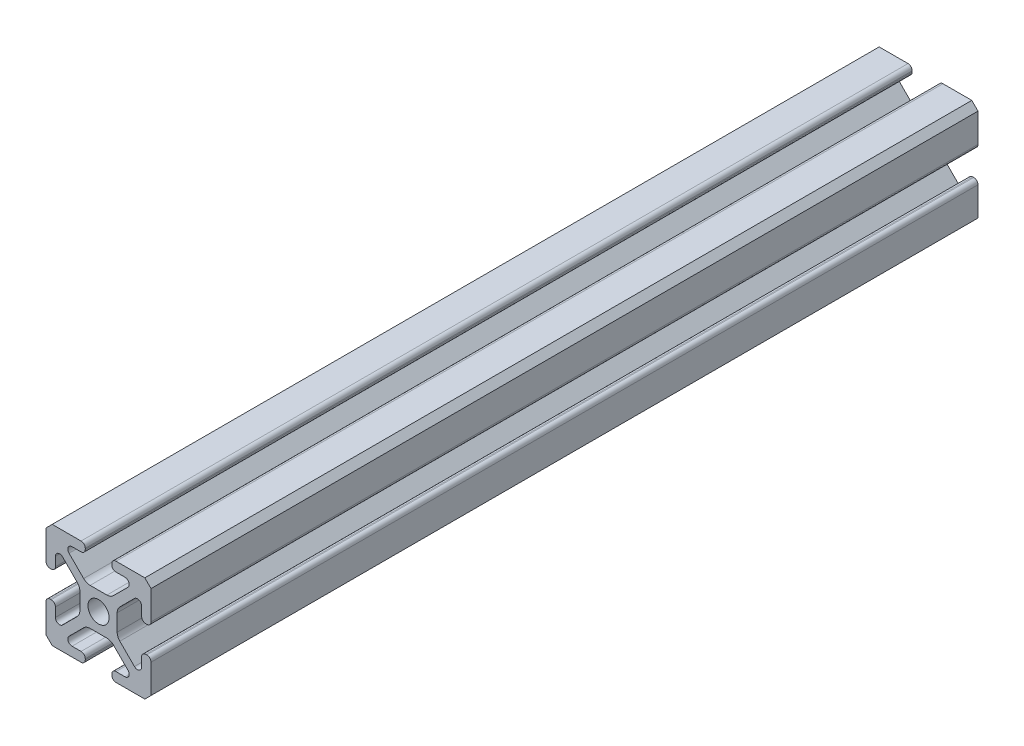
SolidWorks part; units mm, degrees
ref_plane "Front Plane" through (0, 0, 0) normal (0, 0, 1) x (1, 0, 0)
ref_plane "Top Plane" through (0, 0, 0) normal (0, 1, 0) x (1, 0, 0)
ref_plane "Right Plane" through (0, 0, 0) normal (1, 0, 0) x (0, 0, -1)
other "Configuration Table"
sketch "Sketch1" plane through (0, 0, 0) normal (0, 0, 1) x (1, 0, 0)
  line L0 (-11.2, -12.7) -> (-4.2223, -12.7)
  line L1 (-3.2063, -11.684) -> (-3.2063, -11.4407)
  line L2 (-4.2223, -10.4247) -> (-6.4093, -10.4247)
  line L3 (-7.1277, -8.6902) -> (-3.5932, -5.1557)
  line L4 (-2.0306, -4.5085) -> (2.0306, -4.5085)
  line L5 (3.5932, -5.1557) -> (7.1277, -8.6902)
  line L6 (6.4093, -10.4247) -> (4.2223, -10.4247)
  line L7 (3.2063, -11.4407) -> (3.2063, -11.684)
  line L8 (4.2223, -12.7) -> (11.2, -12.7)
  line L9 (11.2, -12.7) -> (12.7, -11.2)
  line L10 (12.7, -11.2) -> (12.7, -4.2223)
  line L11 (11.684, -3.2063) -> (11.4407, -3.2063)
  line L12 (10.4247, -4.2223) -> (10.4247, -6.4093)
  line L13 (8.6902, -7.1277) -> (5.1557, -3.5932)
  line L14 (4.5085, -2.0306) -> (4.5085, 2.0306)
  line L15 (5.1557, 3.5932) -> (8.6902, 7.1277)
  line L16 (10.4247, 6.4093) -> (10.4247, 4.2223)
  line L17 (11.4407, 3.2063) -> (11.684, 3.2063)
  line L18 (12.7, 4.2223) -> (12.7, 11.2)
  line L19 (12.7, 11.2) -> (11.2, 12.7)
  line L20 (11.2, 12.7) -> (4.2223, 12.7)
  line L21 (3.2063, 11.684) -> (3.2063, 11.4407)
  line L22 (4.2223, 10.4247) -> (6.4093, 10.4247)
  line L23 (7.1277, 8.6902) -> (3.5932, 5.1557)
  line L24 (2.0306, 4.5085) -> (-2.0306, 4.5085)
  line L25 (-3.5932, 5.1557) -> (-7.1277, 8.6902)
  line L26 (-6.4093, 10.4247) -> (-4.2223, 10.4247)
  line L27 (-3.2063, 11.4407) -> (-3.2063, 11.684)
  line L28 (-4.2223, 12.7) -> (-11.2, 12.7)
  line L29 (-11.2, 12.7) -> (-12.7, 11.2)
  line L30 (-12.7, 11.2) -> (-12.7, 4.2223)
  line L31 (-11.684, 3.2063) -> (-11.4407, 3.2063)
  line L32 (-10.4247, 4.2223) -> (-10.4247, 6.4093)
  line L33 (-8.6902, 7.1277) -> (-5.1557, 3.5932)
  line L34 (-4.5085, 2.0306) -> (-4.5085, -2.0306)
  line L35 (-5.1557, -3.5932) -> (-8.6902, -7.1277)
  line L36 (-10.4247, -6.4093) -> (-10.4247, -4.2223)
  line L37 (-11.4407, -3.2063) -> (-11.684, -3.2063)
  line L38 (-12.7, -4.2223) -> (-12.7, -11.2)
  line L39 (-12.7, -11.2) -> (-11.2, -12.7)
  arc A0 (-2.555, 0) -> (2.555, 0) centre (0, 0) ccw
  arc A1 (2.555, 0) -> (-2.555, 0) centre (0, 0) ccw
  arc A2 (-4.2223, -12.7) -> (-3.2063, -11.684) centre (-4.2223, -11.684) ccw
  arc A3 (-3.2063, -11.4407) -> (-4.2223, -10.4247) centre (-4.2223, -11.4407) ccw
  arc A4 (-7.1277, -8.6902) -> (-6.4093, -10.4247) centre (-6.4093, -9.4087) ccw
  arc A5 (-2.0306, -4.5085) -> (-3.5932, -5.1557) centre (-2.0306, -6.7183) ccw
  arc A6 (3.5932, -5.1557) -> (2.0306, -4.5085) centre (2.0306, -6.7183) ccw
  arc A7 (7.4253, -9.4087) -> (7.1277, -8.6902) centre (6.4093, -9.4087) ccw
  arc A8 (6.4093, -10.4247) -> (7.4253, -9.4087) centre (6.4093, -9.4087) ccw
  arc A9 (4.2223, -10.4247) -> (3.2063, -11.4407) centre (4.2223, -11.4407) ccw
  arc A10 (3.2063, -11.684) -> (4.2223, -12.7) centre (4.2223, -11.684) ccw
  arc A11 (12.7, -4.2223) -> (11.684, -3.2063) centre (11.684, -4.2223) ccw
  arc A12 (11.4407, -3.2063) -> (10.4247, -4.2223) centre (11.4407, -4.2223) ccw
  arc A13 (8.6902, -7.1277) -> (10.4247, -6.4093) centre (9.4087, -6.4093) ccw
  arc A14 (4.5085, -2.0306) -> (5.1557, -3.5932) centre (6.7183, -2.0306) ccw
  arc A15 (5.1557, 3.5932) -> (4.5085, 2.0306) centre (6.7183, 2.0306) ccw
  arc A16 (9.4087, 7.4253) -> (8.6902, 7.1277) centre (9.4087, 6.4093) ccw
  arc A17 (10.4247, 6.4093) -> (9.4087, 7.4253) centre (9.4087, 6.4093) ccw
  arc A18 (10.4247, 4.2223) -> (11.4407, 3.2063) centre (11.4407, 4.2223) ccw
  arc A19 (11.684, 3.2063) -> (12.7, 4.2223) centre (11.684, 4.2223) ccw
  arc A20 (4.2223, 12.7) -> (3.2063, 11.684) centre (4.2223, 11.684) ccw
  arc A21 (3.2063, 11.4407) -> (4.2223, 10.4247) centre (4.2223, 11.4407) ccw
  arc A22 (7.1277, 8.6902) -> (6.4093, 10.4247) centre (6.4093, 9.4087) ccw
  arc A23 (2.0306, 4.5085) -> (3.5932, 5.1557) centre (2.0306, 6.7183) ccw
  arc A24 (-3.5932, 5.1557) -> (-2.0306, 4.5085) centre (-2.0306, 6.7183) ccw
  arc A25 (-7.4253, 9.4087) -> (-7.1277, 8.6902) centre (-6.4093, 9.4087) ccw
  arc A26 (-6.4093, 10.4247) -> (-7.4253, 9.4087) centre (-6.4093, 9.4087) ccw
  arc A27 (-4.2223, 10.4247) -> (-3.2063, 11.4407) centre (-4.2223, 11.4407) ccw
  arc A28 (-3.2063, 11.684) -> (-4.2223, 12.7) centre (-4.2223, 11.684) ccw
  arc A29 (-12.7, 4.2223) -> (-11.684, 3.2063) centre (-11.684, 4.2223) ccw
  arc A30 (-11.4407, 3.2063) -> (-10.4247, 4.2223) centre (-11.4407, 4.2223) ccw
  arc A31 (-8.6902, 7.1277) -> (-10.4247, 6.4093) centre (-9.4087, 6.4093) ccw
  arc A32 (-4.5085, 2.0306) -> (-5.1557, 3.5932) centre (-6.7183, 2.0306) ccw
  arc A33 (-5.1557, -3.5932) -> (-4.5085, -2.0306) centre (-6.7183, -2.0306) ccw
  arc A34 (-9.4087, -7.4253) -> (-8.6902, -7.1277) centre (-9.4087, -6.4093) ccw
  arc A35 (-10.4247, -6.4093) -> (-9.4087, -7.4253) centre (-9.4087, -6.4093) ccw
  arc A36 (-10.4247, -4.2223) -> (-11.4407, -3.2063) centre (-11.4407, -4.2223) ccw
  arc A37 (-11.684, -3.2063) -> (-12.7, -4.2223) centre (-11.684, -4.2223) ccw
extrude "Boss-Extrude1" add sketch "Sketch1" along normal blind 200
equation "\"Extrusion Length\"= 24"
